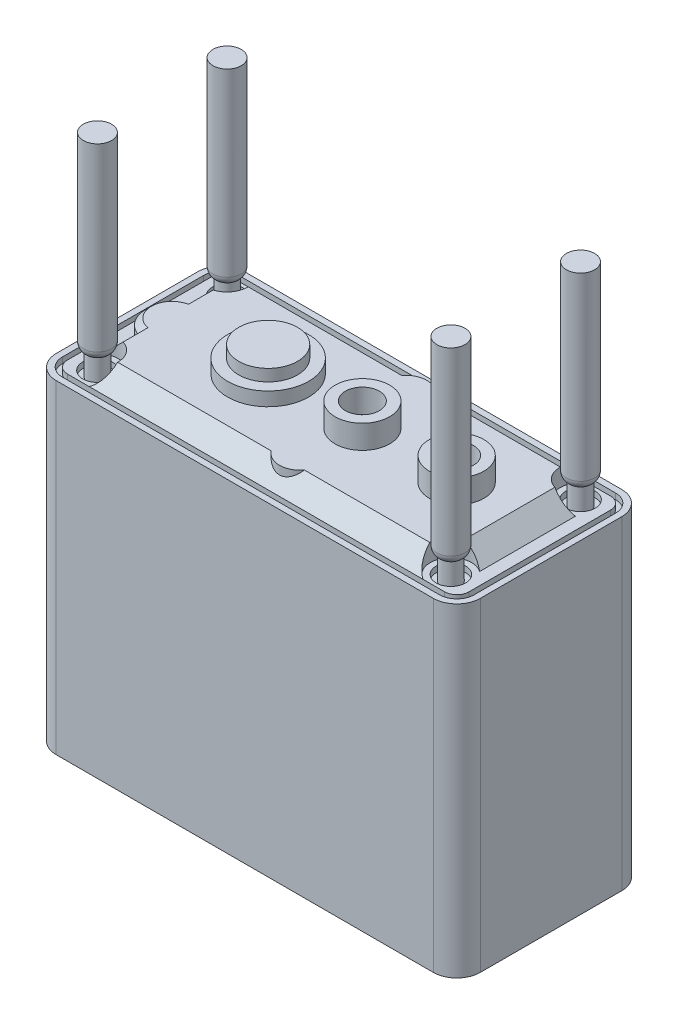
SolidWorks part; units mm, degrees
ref_plane "Front Plane" through (0, 0, 0) normal (0, 0, 1) x (1, 0, 0)
ref_plane "Top Plane" through (0, 0, 0) normal (0, 1, 0) x (1, 0, 0)
ref_plane "Right Plane" through (0, 0, 0) normal (1, 0, 0) x (0, 0, -1)
sketch "Sketch1" plane through (0, 0, 0) normal (0, 1, 0) x (1, 0, 0)
  line L1 (-28.575, 12.7) -> (28.575, 12.7)
  line L2 (-28.575, 12.7) -> (-28.575, -12.7)
  line L3 (-28.575, -12.7) -> (28.575, -12.7)
  line L4 (28.575, 12.7) -> (28.575, -12.7)
  line L5 (-28.575, 12.7) -> (28.575, -12.7) construction
  line L6 (-28.575, -12.7) -> (28.575, 12.7) construction
  point P0 (0, 0)
  dimension "D1" = 57.15
  dimension "D2" = 25.4
extrude "Boss-Extrude1" add sketch "Sketch1" along normal blind 43.6562
fillet "Fillet1" radius 3.175 4 edges at (-28.575, 21.8281, -12.7) (-28.575, 21.8281, 12.7) (28.575, 21.8281, -12.7) (28.575, 21.8281, 12.7)
sketch "Sketch2" plane through (0, 43.6562, 0) normal (0, 1, 0) x (1, 0, 0)
  line L8 (25.4, 11.8745) -> (-25.4, 11.8745)
  line L9 (-27.7495, 9.525) -> (-27.7495, -9.525)
  line L10 (-25.4, -11.8745) -> (25.4, -11.8745)
  line L11 (27.7495, -9.525) -> (27.7495, 9.525)
  line L12 (25.4, 11.8745) -> (-25.4, 11.8745)
  line L13 (-27.7495, 9.525) -> (-27.7495, -9.525)
  line L14 (-25.4, -11.8745) -> (25.4, -11.8745)
  line L15 (27.7495, -9.525) -> (27.7495, 9.525)
  line L20 (25.4, 11.176) -> (-25.4, 11.176)
  line L21 (-27.051, 9.525) -> (-27.051, -9.525)
  line L22 (-25.4, -11.176) -> (25.4, -11.176)
  line L23 (27.051, -9.525) -> (27.051, 9.525)
  line L24 (25.4, 11.176) -> (-25.4, 11.176)
  line L25 (-27.051, 9.525) -> (-27.051, -9.525)
  line L26 (-25.4, -11.176) -> (25.4, -11.176)
  line L27 (27.051, -9.525) -> (27.051, 9.525)
  arc A8 (-25.4, 11.8745) -> (-27.7495, 9.525) centre (-25.4, 9.525) ccw
  arc A9 (-27.7495, -9.525) -> (-25.4, -11.8745) centre (-25.4, -9.525) ccw
  arc A10 (25.4, -11.8745) -> (27.7495, -9.525) centre (25.4, -9.525) ccw
  arc A11 (27.7495, 9.525) -> (25.4, 11.8745) centre (25.4, 9.525) ccw
  arc A12 (-25.4, 11.8745) -> (-27.7495, 9.525) centre (-25.4, 9.525) ccw
  arc A13 (-27.7495, -9.525) -> (-25.4, -11.8745) centre (-25.4, -9.525) ccw
  arc A14 (25.4, -11.8745) -> (27.7495, -9.525) centre (25.4, -9.525) ccw
  arc A15 (27.7495, 9.525) -> (25.4, 11.8745) centre (25.4, 9.525) ccw
  arc A20 (-25.4, 11.176) -> (-27.051, 9.525) centre (-25.4, 9.525) ccw
  arc A21 (-27.051, -9.525) -> (-25.4, -11.176) centre (-25.4, -9.525) ccw
  arc A22 (25.4, -11.176) -> (27.051, -9.525) centre (25.4, -9.525) ccw
  arc A23 (27.051, 9.525) -> (25.4, 11.176) centre (25.4, 9.525) ccw
  arc A24 (-25.4, 11.176) -> (-27.051, 9.525) centre (-25.4, 9.525) ccw
  arc A25 (-27.051, -9.525) -> (-25.4, -11.176) centre (-25.4, -9.525) ccw
  arc A26 (25.4, -11.176) -> (27.051, -9.525) centre (25.4, -9.525) ccw
  arc A27 (27.051, 9.525) -> (25.4, 11.176) centre (25.4, 9.525) ccw
  dimension "D1" = 0.8255
  dimension "D2" = 1.524
extrude "Cut-Extrude1" cut sketch "Sketch2" against normal blind 0.7937
sketch "Sketch3" plane through (0, 43.6562, 0) normal (0, 1, 0) x (1, 0, 0)
  line L1 (23.8125, -8.7312) -> (-23.8125, -8.7313) construction
  line L2 (23.8125, -8.7312) -> (23.8125, 8.7313) construction
  line L3 (23.8125, 8.7313) -> (-23.8125, 8.7312) construction
  line L4 (-23.8125, -8.7313) -> (-23.8125, 8.7312) construction
  line L5 (23.8125, -8.7312) -> (-23.8125, 8.7312) construction
  line L6 (23.8125, 8.7313) -> (-23.8125, -8.7313) construction
  circle A0 centre (-23.8125, 8.7312) radius 1.9844
  circle A1 centre (-23.8125, -8.7313) radius 1.9844
  circle A2 centre (23.8125, -8.7312) radius 1.9844
  circle A3 centre (23.8125, 8.7313) radius 1.9844
  point P0 (0, 0)
  dimension "D1" = 3.9688
  dimension "D2" = 47.625
  dimension "D3" = 17.4625
extrude "Cut-Extrude2" cut sketch "Sketch3" against normal up to surface (0.7937 mm away) up to face at (0, 42.8625, 0)
sketch "Sketch4" plane through (0, 43.6562, 0) normal (0, 1, 0) x (1, 0, 0)
  line L1 (22.493, -11.176) -> (-22.493, -11.176)
  line L2 (25.4, -6.4514) -> (25.4, 6.4514)
  line L3 (22.493, 11.176) -> (-22.493, 11.176)
  line L4 (-25.4, -6.4514) -> (-25.4, 6.4514)
  line L5 (-25.4, -11.176) -> (25.4, -11.176) construction
  line L7 (25.4, 11.176) -> (-25.4, 11.176) construction
  arc A0 (-25.4, 6.4514) -> (-22.493, 11.176) centre (-23.8125, 8.7312) ccw
  arc A1 (-22.493, -11.176) -> (-25.4, -6.4514) centre (-23.8125, -8.7313) ccw
  arc A2 (25.4, -6.4514) -> (22.493, -11.176) centre (23.8125, -8.7312) ccw
  arc A3 (22.493, 11.176) -> (25.4, 6.4514) centre (23.8125, 8.7313) ccw
  point P0 (0, 0)
  dimension "D2" = 5.5562
  dimension "D3" = 50.8
extrude "Boss-Extrude2" add sketch "Sketch4" along normal blind 2.3813
chamfer "Chamfer1" distance 2.3813 angle 45 4 edges at (25.4, 46.0375, 0) (0, 46.0375, -11.176) (-25.4, 46.0375, 0) (0, 46.0375, 11.176)
sketch "Sketch5" plane through (0, 46.0375, 0) normal (0, 1, 0) x (1, 0, 0)
  line L0 (-28.575, 9.525) -> (-28.575, -9.525) construction
  line L1 (1.905, -7.1437) -> (1.905, 0) construction
  line L2 (1.905, 0) -> (1.905, 7.1437) construction
  line L3 (-23.0187, 6.0689) -> (-23.0187, -6.0689) construction
  circle A0 centre (1.905, 7.1437) radius 2.7781
  circle A1 centre (1.905, -7.1437) radius 2.7781
  circle A2 centre (-22.5107, 0) radius 3.5719
  dimension "D2" = 5.5562
  dimension "D4" = 7.1437
  dimension "D1" = 30.48
  dimension "D3" = 7.1437
  dimension "D5" = 0.508
extrude "Boss-Extrude3" add sketch "Sketch5" against normal up to surface (2.3813 mm away) up to face at (-23.8125, 43.6562, -6.7469)
chamfer "Chamfer2" distance 0.7937 angle 45 1 edges at (-26.0826, 46.0375, 0)
sketch "Sketch6" plane through (0, 46.0375, 0) normal (0, 1, 0) x (1, 0, 0)
  line L0 (-9.5491, 0) -> (3.1509, 0) construction
  line L1 (3.1509, 0) -> (15.8509, 0) construction
  line L2 (28.575, -9.525) -> (28.575, 9.525) construction
  circle A0 centre (3.1509, 0) radius 3.683
  circle A1 centre (3.1509, 0) radius 2.286
  circle A2 centre (15.8509, 0) radius 3.683
  circle A3 centre (15.8509, 0) radius 2.286
  circle A4 centre (-9.5491, 0) radius 5.461 construction
  dimension "D1" = 10.922
  dimension "D3" = 7.366
  dimension "D4" = 4.572
  dimension "D2" = 12.7
  dimension "D5" = 12.7241
extrude "Boss-Extrude4" add sketch "Sketch6" along normal blind 3.175
sketch "Sketch7" plane through (0, 46.0375, 0) normal (0, 1, 0) x (1, 0, 0)
  circle A0 centre (-9.5491, 0) radius 5.461 construction
  circle A1 centre (-9.5491, 0) radius 5.461
extrude "Boss-Extrude5" add sketch "Sketch7" along normal blind 3.429
sketch "Sketch8" plane through (0, 42.8625, 0) normal (0, 1, 0) x (1, 0, 0)
  circle A0 centre (-23.8125, -8.7313) radius 1.27
  circle A1 centre (23.8125, -8.7312) radius 1.27
  circle A2 centre (23.8125, 8.7313) radius 1.27
  circle A3 centre (-23.8125, 8.7312) radius 1.27
  dimension "D1" = 2.54
extrude "Boss-Extrude6" add sketch "Sketch8" along normal blind 3.175
sketch "Sketch9" plane through (0, 46.0375, 0) normal (0, 1, 0) x (1, 0, 0)
  circle A0 centre (-23.8125, -8.7313) radius 1.905
  circle A1 centre (-23.8125, 8.7312) radius 1.905
  circle A2 centre (23.8125, 8.7313) radius 1.905
  circle A3 centre (23.8125, -8.7312) radius 1.905
  dimension "D1" = 3.81
extrude "Boss-Extrude7" add sketch "Sketch9" along normal blind 25.4
fillet "Fillet2" radius 1.27 4 edges at (-23.8125, 46.0375, -6.8262) (23.8125, 46.0375, -6.8263) (23.8125, 46.0375, 10.6362) (-23.8125, 46.0375, 10.6363)
sketch "Sketch10" plane through (0, 49.4665, 0) normal (0, 1, 0) x (1, 0, 0)
  circle A0 centre (-9.5491, 0) radius 3.9688
  circle A1 centre (-9.5491, 0) radius 5.461
  circle A2 centre (-9.5491, 0) radius 5.461
  dimension "D2" = 7.9375
  dimension "D1" = 0
extrude "Cut-Extrude3" cut sketch "Sketch10" against normal blind 1.5875
